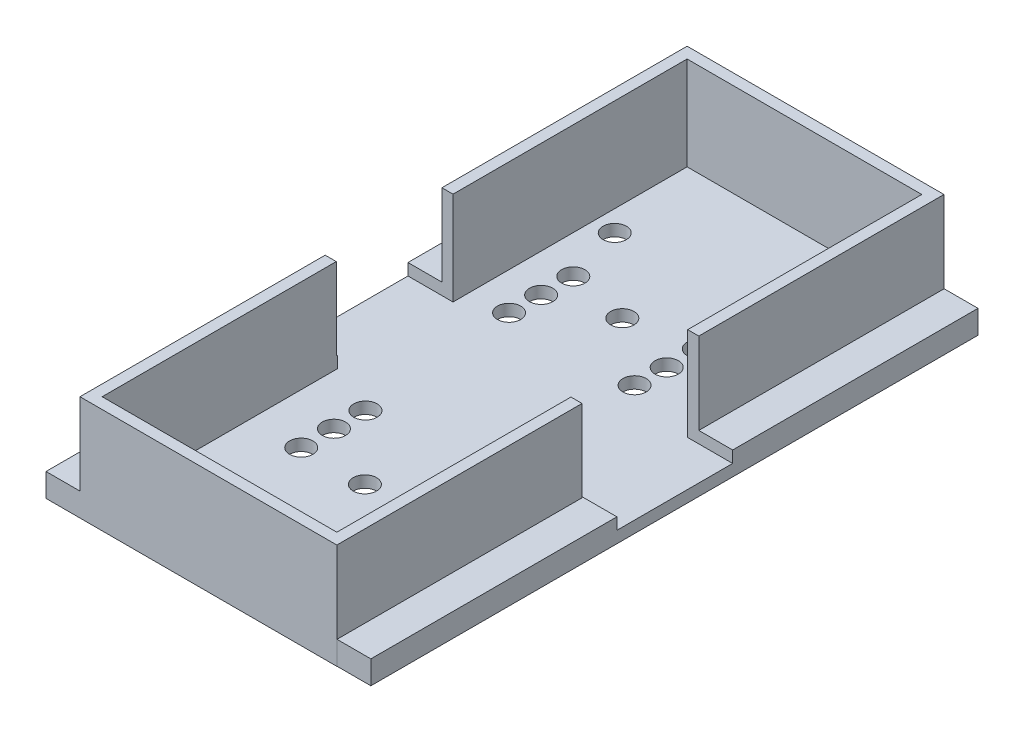
SolidWorks part; units mm, degrees
ref_plane "Front Plane" through (0, 0, 0) normal (0, 0, 1) x (1, 0, 0)
ref_plane "Top Plane" through (0, 0, 0) normal (0, 1, 0) x (1, 0, 0)
ref_plane "Right Plane" through (0, 0, 0) normal (1, 0, 0) x (0, 0, -1)
sketch "Sketch1" plane through (0, 0, 0) normal (0, 1, 0) x (1, 0, 0)
  line L1 (-11, -26) -> (11, -26)
  line L2 (-11, -26) -> (-11, 26)
  line L3 (-11, 26) -> (11, 26)
  line L4 (11, -26) -> (11, 26)
  line L5 (-11, -26) -> (11, 26) construction
  line L6 (-11, 26) -> (11, -26) construction
  point P0 (0, 0)
  dimension "D1" = 52
  dimension "D2" = 22
extrude "Boss-Extrude1" add sketch "Sketch1" along normal blind 9
sketch "Sketch2" plane through (0, 9, 0) normal (0, 1, 0) x (1, 0, 0)
  line L0 (-11, -26) -> (11, -26) construction
  line L1 (-10.05, -25.05) -> (10.05, -25.05)
  line L2 (-10.05, -25.05) -> (-10.05, 25.05)
  line L3 (-10.05, 25.05) -> (10.05, 25.05)
  line L4 (10.05, -25.05) -> (10.05, 25.05)
  line L5 (-10.05, -25.05) -> (10.05, 25.05) construction
  line L6 (-10.05, 25.05) -> (10.05, -25.05) construction
  line L8 (11, -26) -> (11, 26) construction
  point P0 (0, 0)
  dimension "D1" = 0.95
  dimension "D2" = 0.95
extrude "Cut-Extrude1" cut sketch "Sketch2" against normal blind 10 from offset 2
sketch "Sketch3" plane through (0, 0, 0) normal (0, -1, 0) x (1, 0, 0)
  line L0 (0, -25) -> (0, 25) construction
  line L1 (-10, 0) -> (10, 0) construction
  line L2 (11, 26) -> (11, -26) construction
  line L3 (-11, -26) -> (-11, 26) construction
  line L4 (-11, 26) -> (11, 26) construction
  line L5 (11, -26) -> (-11, -26) construction
  line L6 (0, -23) -> (-10, -23) construction
  line L7 (-4.5, -25) -> (-7.5, -24) construction
  point P21 (-6, -24.5)
  dimension "D1" = 1
  dimension "D2" = 1
  dimension "D3" = 1
  dimension "D4" = 1
  dimension "D5" = 2
  dimension "D10" = 6
sketch "Sketch7" plane through (0, 1, 0) normal (0, 1, 0) x (1, 0, 0)
  line L0 (-10.05, 25.05) -> (-10.05, -25.05) construction
  line L3 (-10.05, -25.05) -> (10.05, -25.05) construction
  circle A0 centre (-8.15, -23) radius 0.8
  dimension "D1" = 1.6
  dimension "D2" = 1.9
  dimension "D3" = 2.05
extrude "Cut-Extrude6" cut sketch "Sketch7" against normal through all both and the other way through all
sketch "Sketch8" plane through (0, 1, 0) normal (0, 1, 0) x (1, 0, 0)
  line L0 (-10.05, 25.05) -> (-10.05, -25.05) construction
  line L1 (-10.05, -25.05) -> (10.05, -25.05) construction
  circle A0 centre (-5.75, -12.3) radius 1
  circle A2 centre (5, -12.3) radius 1
  dimension "D1" = 4.3
  dimension "D2" = 12.75
  dimension "D3" = 10.75
extrude "Cut-Extrude7" cut sketch "Sketch8" against normal up to next
sketch "Sketch9" plane through (0, 1, 0) normal (0, 1, 0) x (1, 0, 0)
  line L0 (-10.05, 25.05) -> (-10.05, -25.05) construction
  line L1 (-10.05, -25.05) -> (10.05, -25.05) construction
  circle A0 centre (-5.75, -9.5) radius 1
  circle A1 centre (5, -9.5) radius 1
  dimension "D1" = 4.3
  dimension "D2" = 15.55
  dimension "D3" = 10.75
extrude "Cut-Extrude9" cut sketch "Sketch9" against normal up to next
sketch "Sketch10" plane through (0, 1, 0) normal (0, 1, 0) x (1, 0, 0)
  line L0 (-10.05, 25.05) -> (-10.05, -25.05) construction
  line L1 (-10.05, -25.05) -> (10.05, -25.05) construction
  circle A0 centre (-5.75, -6.8) radius 1
  circle A1 centre (5, -6.8372) radius 1
  dimension "D1" = 4.3
  dimension "D2" = 18.25
  dimension "D3" = 10.75
extrude "Cut-Extrude10" cut sketch "Sketch10" against normal up to next
sketch "Sketch11" plane through (0, 1, 0) normal (0, 1, 0) x (1, 0, 0)
  line L0 (-10.05, -25.05) -> (10.05, -25.05) construction
  line L1 (-10.05, 25.05) -> (-10.05, -25.05) construction
  circle A0 centre (-0.3, -12.3) radius 1
  dimension "D1" = 12.75
  dimension "D2" = 9.75
extrude "Cut-Extrude11" cut sketch "Sketch11" against normal up to next
sketch "Sketch12" plane through (0, 1, 0) normal (0, 1, 0) x (1, 0, 0)
  line L0 (10.05, 25.05) -> (-10.05, 25.05) construction
  line L1 (10.05, -25.05) -> (10.05, 25.05) construction
  circle A0 centre (3.95, 12.05) radius 1
  circle A1 centre (-6.8, 12.05) radius 1
  dimension "D1" = 13
  dimension "D2" = 6.1
  dimension "D3" = 10.75
extrude "Cut-Extrude12" cut sketch "Sketch12" against normal up to next
sketch "Sketch13" plane through (0, 1, 0) normal (0, 1, 0) x (1, 0, 0)
  line L0 (10.05, 25.05) -> (-10.05, 25.05) construction
  line L1 (10.05, -25.05) -> (10.05, 25.05) construction
  circle A0 centre (3.95, 9.3) radius 1
  circle A1 centre (-6.8, 9.3) radius 1
  dimension "D1" = 15.75
  dimension "D2" = 6.1
  dimension "D3" = 10.75
extrude "Cut-Extrude13" cut sketch "Sketch13" against normal up to next
sketch "Sketch14" plane through (0, 1, 0) normal (0, 1, 0) x (1, 0, 0)
  line L0 (10.05, 25.05) -> (-10.05, 25.05) construction
  line L1 (10.05, -25.05) -> (10.05, 25.05) construction
  circle A0 centre (3.9, 6.6) radius 1
  circle A1 centre (-6.85, 6.6) radius 1
  dimension "D1" = 18.45
  dimension "D2" = 6.15
  dimension "D3" = 10.75
extrude "Cut-Extrude14" cut sketch "Sketch14" against normal up to next
sketch "Sketch15" plane through (0, 1, 0) normal (0, 1, 0) x (1, 0, 0)
  line L0 (10.05, 25.05) -> (-10.05, 25.05) construction
  line L1 (-10.05, 25.05) -> (-10.05, -25.05) construction
  circle A0 centre (-1.6, 11.05) radius 1
  dimension "D1" = 14
  dimension "D2" = 8.45
extrude "Cut-Extrude15" cut sketch "Sketch15" against normal up to next
sketch "Sketch16" plane through (0, 1, 0) normal (0, 1, 0) x (1, 0, 0)
  line L0 (10.05, 25.05) -> (-10.05, 25.05) construction
  line L1 (-10.05, 25.05) -> (-10.05, -25.05) construction
  circle A0 centre (-8.25, 17.05) radius 1
  dimension "D1" = 8
  dimension "D2" = 1.8
extrude "Cut-Extrude16" cut sketch "Sketch16" against normal up to next
sketch "Sketch18" plane through (0, 0, 0) normal (0, -1, 0) x (1, 0, 0)
  line L0 (-11, -26) -> (-13.9, -26)
  line L1 (-11, -26) -> (-13.91, -26)
  line L2 (-11, -26) -> (-11, 26)
  line L3 (-11, 26) -> (-13.91, 26)
  line L4 (-13.91, -26) -> (-13.91, 26)
  line L5 (-11, -26) -> (-11, 26)
  line L6 (-11, 26) -> (-13.9, 26)
  line L7 (-13.9, -26) -> (-13.9, 26)
  line L8 (13.9, -26.013) -> (11, -26.013)
  line L9 (13.9, -26.013) -> (13.9, 25.987)
  line L10 (13.9, 25.987) -> (11, 25.987)
  line L11 (11, -26.013) -> (11, 25.987)
  dimension "D1" = 2.91
  dimension "D2" = 52
  dimension "D3" = 22
extrude "Boss-Extrude2" add sketch "Sketch18" against normal blind 2 contours L4 L3 L2 L1
extrude "Boss-Extrude3" add sketch "Sketch18<3>" against normal blind 2 contours L9 L10 L11 L8
sketch "Sketch18<3>" plane through (0, 0, 0) normal (0, -1, 0) x (1, 0, 0) same geometry as "Sketch18"
sketch "Sketch19" plane through (-11, 0, 0) normal (-1, 0, 0) x (0, 0, 1)
  line L0 (-26, 9) -> (26, 9) construction
  line L1 (-5, 9) -> (5, 9)
  line L2 (-5, 9) -> (-5, 2)
  line L3 (-5, 2) -> (5, 2)
  line L4 (5, 9) -> (5, 2)
  line L5 (-26, 2) -> (26, 2) construction
  line L6 (-26, 9) -> (-26, 2) construction
  dimension "D1" = 10
  dimension "D2" = 21
extrude "Cut-Extrude17" cut sketch "Sketch19" against normal through all
sketch "Sketch20" plane through (0, 2, 0) normal (0, 1, 0) x (1, 0, 0)
  line L0 (-13.91, 26) -> (-13.91, -26) construction
  line L1 (-10.05, 5) -> (-13.91, 5)
  line L2 (-10.05, 5) -> (-10.05, -4.9153)
  line L3 (-10.05, -4.9153) -> (-13.91, -4.9153)
  line L4 (-13.91, 5) -> (-13.91, -4.9153)
  line L5 (10.05, -25.05) -> (10.05, 25.05) construction
  line L6 (10.05, 5) -> (14.3577, 5)
  line L7 (10.05, 5) -> (10.05, -4.9153)
  line L8 (10.05, -4.9153) -> (14.3577, -4.9153)
  line L9 (14.3577, 5) -> (14.3577, -4.9153)
extrude "Cut-Extrude18" cut sketch "Sketch20" against normal blind 1
